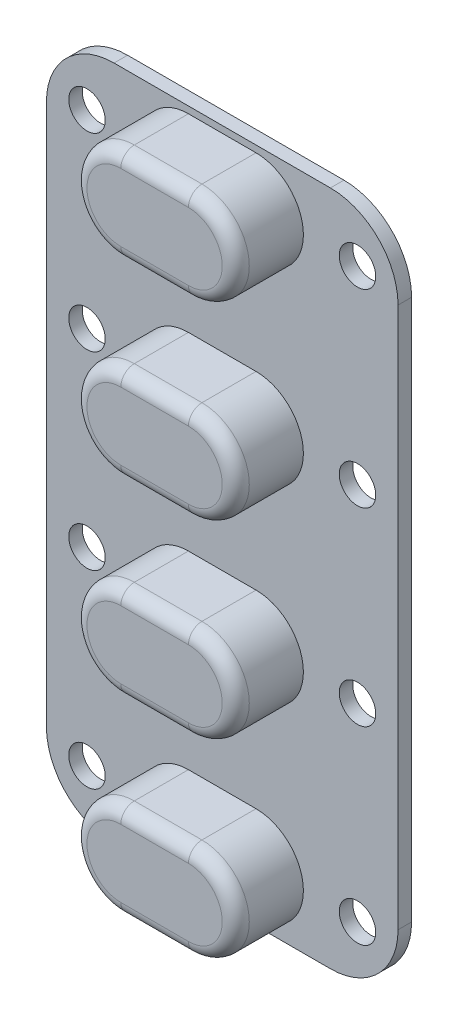
SolidWorks part; units mm, degrees
ref_plane "Front Plane" through (0, 0, 0) normal (0, 0, 1) x (1, 0, 0)
ref_plane "Top Plane" through (0, 0, 0) normal (0, 1, 0) x (1, 0, 0)
ref_plane "Right Plane" through (0, 0, 0) normal (1, 0, 0) x (0, 0, -1)
sketch "Sketch1" plane through (0, 0, 0) normal (0, 0, 1) x (1, 0, 0)
  line L1 (13, 25) -> (-13, 25)
  line L2 (13, 25) -> (13, -25)
  line L3 (13, -25) -> (-13, -25)
  line L4 (-13, 25) -> (-13, -25)
  line L5 (13, 25) -> (-13, -25) construction
  line L6 (13, -25) -> (-13, 25) construction
  circle A1 centre (10, -21) radius 1.35
  circle A9 centre (10, -7) radius 1.35
  circle A10 centre (10, 7) radius 1.35
  circle A11 centre (10, 21) radius 1.35
  circle A12 centre (-10, -7) radius 1.35
  circle A13 centre (-10, 7) radius 1.35
  circle A14 centre (-10, 21) radius 1.35
  circle A15 centre (-10, -21) radius 1.35
  point P0 (0, 0)
  dimension "D5" = 2.7
  dimension "D1" = 26
  dimension "D2" = 50
  dimension "D3" = 10
  dimension "D4" = 21
  dimension "D8" = 14
  dimension "D9" = 20
  dimension "D6" = 4
  dimension "D7" = 2
extrude "Boss-Extrude1" add sketch "Sketch1" along normal blind 1
sketch "Sketch2" plane through (0, 0, 1) normal (0, 0, 1) x (1, 0, 0)
  line L0 (-2.5, 21) -> (2.5, 21) construction
  line L1 (-2.5, 24.5) -> (2.5, 24.5)
  line L2 (-2.5, 17.5) -> (2.5, 17.5)
  line L3 (-2.5, 3.5) -> (2.5, 3.5)
  line L4 (-2.5, 10.5) -> (2.5, 10.5)
  line L5 (-2.5, 7) -> (2.5, 7) construction
  line L6 (-2.5, -10.5) -> (2.5, -10.5)
  line L7 (-2.5, -3.5) -> (2.5, -3.5)
  line L8 (-2.5, -7) -> (2.5, -7) construction
  line L9 (-2.5, -24.5) -> (2.5, -24.5)
  line L10 (-2.5, -17.5) -> (2.5, -17.5)
  line L11 (-2.5, -21) -> (2.5, -21) construction
  arc A0 (-2.5, 24.5) -> (-2.5, 17.5) centre (-2.5, 21) ccw
  arc A1 (2.5, 17.5) -> (2.5, 24.5) centre (2.5, 21) ccw
  arc A2 (-2.5, 10.5) -> (-2.5, 3.5) centre (-2.5, 7) ccw
  arc A3 (2.5, 3.5) -> (2.5, 10.5) centre (2.5, 7) ccw
  arc A4 (-2.5, -3.5) -> (-2.5, -10.5) centre (-2.5, -7) ccw
  arc A5 (2.5, -10.5) -> (2.5, -3.5) centre (2.5, -7) ccw
  arc A6 (-2.5, -17.5) -> (-2.5, -24.5) centre (-2.5, -21) ccw
  arc A7 (2.5, -24.5) -> (2.5, -17.5) centre (2.5, -21) ccw
  point P2 (0, 21)
  point P10 (0, 7)
  point P18 (0, -7)
  point P25 (0, -21)
  dimension "D2" = 3.5
  dimension "D1" = 5
  dimension "D3" = 21
  dimension "D5" = 14
  dimension "D4" = 4
extrude "Boss-Extrude2" add sketch "Sketch2" along normal blind 5
fillet "Fillet1" radius 1 16 edges at (0, -17.5, 6) (6, -21, 6) (0, -24.5, 6) (-6, -21, 6) (0, -3.5, 6) (6, -7, 6) (0, -10.5, 6) (-6, -7, 6) (0, 10.5, 6) (6, 7, 6) (0, 3.5, 6) (-6, 7, 6) (0, 24.5, 6) (6, 21, 6) (0, 17.5, 6) (-6, 21, 6)
fillet "Fillet2" radius 5 4 edges at (13, 25, 0.5) (-13, 25, 0.5) (13, -25, 0.5) (-13, -25, 0.5)
sketch "Sketch3" plane through (0, 0, 0) normal (0, 0, -1) x (-1, 0, 0)
  line L0 (10, 21) -> (-10, 21) construction
  line L1 (-10, 7) -> (10, 7) construction
  line L2 (10, -7) -> (-10, -7) construction
  line L3 (-10, -21) -> (10, -21) construction
  circle A0 centre (0, 21) radius 2.5
  circle A1 centre (0, 7) radius 2.5
  circle A2 centre (0, -7) radius 2.5
  circle A3 centre (0, -21) radius 2.5
  dimension "D1" = 5
extrude "Cut-Extrude1" cut sketch "Sketch3" against normal blind 3 contours A0 | A1 | A2 | A3 region at (0, 21, 0) region at (0, 7, 0) region at (0, -7, 0) region at (0, -21, 0)
